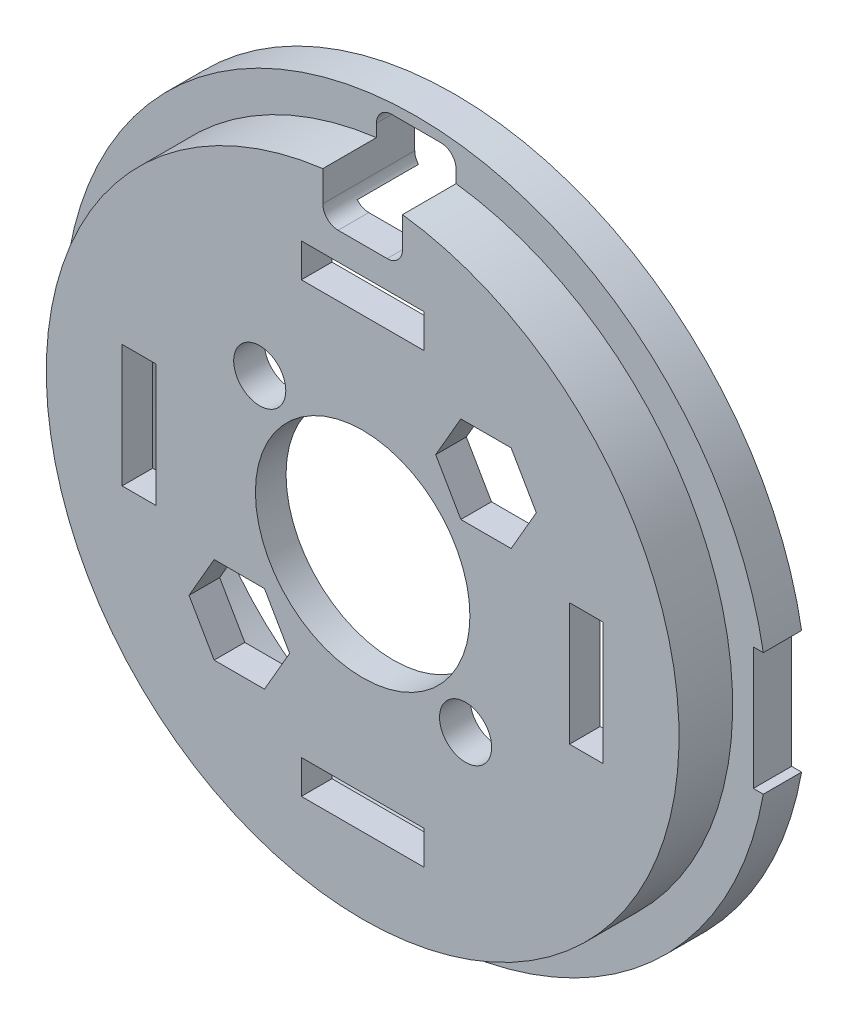
SolidWorks part; units mm, degrees
other "标注1"
sketch "草图10" plane through (17.4, 17.4, 7.6) normal (0.4476, 0.4282, 0.7851) x (0.8625, 0.025, -0.5054)
ref_plane "前视基准面" through (0, 0, 0) normal (0, 0, 1) x (1, 0, 0)
ref_plane "上视基准面" through (0, 0, 0) normal (0, 1, 0) x (1, 0, 0)
ref_plane "右视基准面" through (0, 0, 0) normal (1, 0, 0) x (0, 0, -1)
other "Configuration Table"
sketch "草图1" plane through (0, 0, 0) normal (0, 0, 1) x (1, 0, 0)
  circle A0 centre (0, 0) radius 17.4
  dimension "D1" = 34.8
extrude "凸台-拉伸1" add sketch "草图1" along normal blind 5.6
sketch "草图2" plane through (0, 0, 5.6) normal (0, 0, 1) x (1, 0, 0)
  line L0 (5.5154, -5.5154) -> (6.7175, -6.7175) construction
  line L1 (-6.7175, 6.7175) -> (-5.0175, 6.7175)
  line L2 (-6.7175, 6.7175) -> (-6.7175, 5.0175)
  line L3 (5.0175, -6.7175) -> (6.7175, -6.7175)
  line L4 (6.7175, -5.0175) -> (6.7175, -6.7175)
  line L5 (-6.7175, 6.7175) -> (-0.0325, 0.0325) construction
  line L6 (-6.7175, 6.7175) -> (6.7175, -6.7175)
  circle A0 centre (-6.7175, 6.7175) radius 1.7
  circle A2 centre (6.7175, -6.7175) radius 1.7
  arc A4 (-5.5154, -5.5154) -> (-6.7175, -5.0175) centre (-6.7175, -6.7175) ccw [skipped]
  arc A5 (5.0175, 6.7175) -> (5.5154, 5.5154) centre (6.7175, 6.7175) ccw [skipped]
  point P0 (0, 0)
  point P16 (0, 0)
  dimension "D3" = 3.4
  dimension "D1" = 19
  dimension "D2" = 9.5
  dimension "D4" = 4
extrude "切除-拉伸1" cut sketch "草图2" against normal through all contours A0 | A2
sketch "草图3" plane through (0, 0, 5.6) normal (0, 0, 1) x (1, 0, 0)
  circle A0 centre (0, 0) radius 7
  dimension "D1" = 14
extrude "切除-拉伸2" cut sketch "草图3" against normal through all
sketch "草图4" plane through (0, 0, 5.6) normal (0, 0, 1) x (1, 0, 0)
  circle A1 centre (-6.7175, 6.7175) radius 2.8
  circle A2 centre (6.7175, -6.7175) radius 2.8
  dimension "D1" = 5.6
  dimension "D2" = 5.6
extrude "切除-拉伸3" cut sketch "草图4" against normal blind 3
sketch "草图5" plane through (0, 0, 5.6) normal (0, 0, 1) x (1, 0, 0)
  line L1 (-8.05, 8) -> (8.05, 8)
  line L2 (-8.05, 8) -> (-8.05, -8)
  line L3 (-8.05, -8) -> (8.05, -8)
  line L4 (8.05, 8) -> (8.05, -8)
  line L5 (-8.05, 8) -> (8.05, -8) construction
  line L6 (-8.05, -8) -> (8.05, 8) construction
  circle A0 centre (8.05, 8) radius 1.7
  circle A1 centre (-8.05, -8) radius 1.7
  point P0 (0, 0)
  dimension "D3" = 3.4
  dimension "D4" = 3.4
  dimension "D1" = 16.1
  dimension "D2" = 16
extrude "切除-拉伸4" cut sketch "草图5" against normal through all contours A1 | A0
sketch "草图6" plane through (0, 0, 0) normal (0, 0, -1) x (-1, 0, 0)
  line L0 (4.7668, -8) -> (6.4084, -10.8433)
  line L1 (-4.7668, 8) -> (-6.4084, 10.8433)
  line L2 (-6.4084, 10.8433) -> (-9.6916, 10.8433)
  line L3 (-9.6916, 10.8433) -> (-11.3332, 8)
  line L4 (-11.3332, 8) -> (-9.6916, 5.1567)
  line L5 (-9.6916, 5.1567) -> (-6.4084, 5.1567)
  line L6 (-6.4084, 5.1567) -> (-4.7668, 8)
  line L7 (6.4084, -10.8433) -> (9.6916, -10.8433)
  line L8 (9.6916, -10.8433) -> (11.3332, -8)
  line L9 (11.3332, -8) -> (9.6916, -5.1567)
  line L10 (9.6916, -5.1567) -> (6.4084, -5.1567)
  line L11 (6.4084, -5.1567) -> (4.7668, -8)
  circle A0 centre (-8.05, 8) radius 2.8433 construction
  point P17 (0, 0)
  dimension "D1" = 2
extrude "切除-拉伸5" cut sketch "草图6" against normal blind 2.5
sketch "草图7" plane through (0, 0, 5.6) normal (0, 0, 1) x (1, 0, 0)
  line L5 (-8.05, 8.05) -> (8.05, 8.05)
  line L6 (-8.05, 8.05) -> (-8.05, -8.05)
  line L11 (-8.05, -8.05) -> (8.05, -8.05)
  line L12 (8.05, 8.05) -> (8.05, -8.05)
  line L13 (-8.05, 8.05) -> (8.05, -8.05) construction
  line L14 (-8.05, -8.05) -> (8.05, 8.05) construction
  point P0 (0, 0)
  dimension "D1" = 16.1
  dimension "D2" = 16.1
extrude "切除-拉伸6" cut sketch "草图7" against normal blind 1.5
chamfer "倒角1" distance 0.5 angle 45 4 edges at (1.0479, 8.05, 5.6) (8.05, 1.0226, 5.6) (-1.0479, -8.05, 5.6) (-8.05, -1.0226, 5.6)
sketch "草图8" plane through (0, 0, 0) normal (1, 0, 0) x (0, 0, -1)
  line L0 (0, 17.4) -> (0, 17.2)
  line L1 (0, 17.4) -> (0.2, 17.4)
  line L2 (0.2, 17.4) -> (0, 17.2)
  dimension "D1" = 0.2
  dimension "D2" = 0.2
ref_axis "基准轴1" through (0, 0, 0) along (0, 0, 1)
revolve "旋转1" add sketch "草图8" angle 360 about axis through (0, 0, 0) along (0, 0, 1)
sketch "草图9" plane through (0, 0, 5.6) normal (0, 0, 1) x (1, 0, 0)
  line L0 (0, 0) -> (15, 0) construction
  line L1 (4, -13.5) -> (-4, -13.5)
  line L2 (13.5, 4) -> (16.5, 4)
  line L3 (13.5, 4) -> (13.5, -4)
  line L4 (13.5, -4) -> (16.5, -4)
  line L5 (16.5, 4) -> (16.5, -4)
  line L6 (13.5, 4) -> (16.5, -4) construction
  line L7 (13.5, -4) -> (16.5, 4) construction
  line L8 (4, -13.5) -> (4, -16.5)
  line L9 (4, -16.5) -> (-4, -16.5)
  line L10 (-4, -13.5) -> (-4, -16.5)
  line L11 (-13.5, -4) -> (-13.5, 4)
  line L12 (-13.5, -4) -> (-16.5, -4)
  line L13 (-16.5, -4) -> (-16.5, 4)
  line L14 (-13.5, 4) -> (-16.5, 4)
  line L15 (-4, 13.5) -> (4, 13.5)
  line L16 (-4, 13.5) -> (-4, 16.5)
  line L17 (-4, 16.5) -> (4, 16.5)
  line L18 (4, 13.5) -> (4, 16.5)
  line L19 (15.7, 4) -> (15.7, -4)
  line L20 (4, -15.7) -> (-4, -15.7)
  line L21 (-15.7, -4) -> (-15.7, 4)
  line L22 (-4, 15.7) -> (4, 15.7)
  point P22 (0, 0)
  point P31 (0, 0)
  dimension "D1" = 15
  dimension "D2" = 3
  dimension "D3" = 8
  dimension "D5" = 0.8
  dimension "D4" = 4
  dimension "D6" = 4
extrude "切除-拉伸7" cut sketch "草图9" against normal through all contours L19 L2 L3 L4 | L22 L16 L15 L18 | L21 L12 L11 L14 | L20 L8 L1 L10 region at (0, -14.6, 5.6) region at (14.6, 0, 5.6) region at (-14.6, 0, 5.6) region at (0, 14.6, 5.6)
sketch "Sketch1" plane through (0, 0, 0) normal (0, 0, 1) x (1, 0, 0)
  circle A0 centre (0, 0) radius 17.4
  circle A1 centre (0, 0) radius 20.65
  dimension "D1" = 41.3
extrude "Boss-Extrude1" add sketch "Sketch1" along normal up to surface (5.6 mm away) and the other way blind 4 up to face at (0, 0, 5.6)
sketch "Sketch2" plane through (0, 0, -4) normal (0, 0, -1) x (-1, 0, 0)
  line L0 (0, 0) -> (-17.5, 0)
  line L1 (-17.5, 0) -> (-17.5, 4)
  line L2 (-17.5, 4) -> (-20, 4)
  line L3 (-20, 4) -> (-20, -4)
  line L4 (-20, -4) -> (-17.5, -4)
  line L5 (-17.5, -4) -> (-17.5, 0)
  dimension "D1" = 2.5
  dimension "D2" = 4
  dimension "D3" = 4
  dimension "D4" = 17.5
sketch "Sketch3" plane through (0, 0, -4) normal (0, 0, -1) x (-1, 0, 0)
  circle A0 centre (0, 0) radius 20.65
  circle A1 centre (0, 0) radius 23
  circle M10 centre (0, 0) radius 20.65
  dimension "D1" = 46
extrude "Boss-Extrude2" add sketch "Sketch3" against normal blind 2.5 contours A1 M10 region at (22.3495, 0, -4)
sketch "Sketch4" plane through (0, 0, -4) normal (0, 0, -1) x (-1, 0, 0)
  circle A0 centre (0, 0) radius 18
  dimension "D1" = 36
extrude "Cut-Extrude3" cut sketch "Sketch4" against normal up to surface (4 mm away) up to face at (0, 14.6, 0)
sketch "Sketch5" plane through (0, 0, -4) normal (0, 0, -1) x (-1, 0, 0)
  line L13 (0, 0) -> (23, 0)
  line L14 (0, 0) -> (-23, 0)
  line L15 (23, -4) -> (22, -4)
  line L16 (23, -4) -> (23, 4)
  line L17 (23, 4) -> (22, 4)
  line L18 (22, -4) -> (22, 4)
  line L19 (-23, 4) -> (-22, 4)
  line L20 (-23, 4) -> (-23, -4)
  line L21 (-23, -4) -> (-22, -4)
  line L22 (-22, 4) -> (-22, -4)
  circle A0 centre (0, 0) radius 23 construction
  point P9 (0, 22)
  point P19 (0, -22)
  point P23 (0, 0)
  point P34 (0, 0)
  dimension "D4" = 8
  dimension "D5" = 1
  dimension "D6" = 4
  dimension "D3" = 2
  dimension "D7" = 2
extrude "Cut-Extrude4" cut sketch "Sketch5" against normal blind 10 contours L19 L22 L21 L20 | L16 L15 L18 L17
sketch "Sketch7" plane through (0, 0, -4) normal (0, 0, -1) x (-1, 0, 0)
  line L1 (0, 22.3) -> (2.6, 22.3)
  line L2 (0, 17.5) -> (-2.6, 17.5)
  line L3 (0, 17.5) -> (0, 22.3)
  line L4 (0, 22.3) -> (-2.6, 22.3)
  line L5 (-2.6, 17.5) -> (-2.6, 22.3)
  line L7 (0, 22.3) -> (0, 17.5)
  line L10 (0, 22.3) -> (0, 17.5)
  line L11 (0, 17.5) -> (2.6, 17.5)
  line L12 (2.6, 22.3) -> (2.6, 17.5)
  circle M5 centre (0, 0) radius 18
  dimension "D1" = 2.6
  dimension "D2" = 2.6
  dimension "D3" = 4.8
extrude "Cut-Extrude6" cut sketch "Sketch7" against normal blind 10 contours L5 L3 L4 M5 | L5 L2 L3 M5 | L12 L1 L3 M5 | L12 L3 L11 M5 region at (-1.3094, 20.1182, -4) region at (1.3094, 20.1182, -4) region at (-1.2066, 17.7222, -4) region at (1.2066, 17.7222, -4)
fillet "Fillet3" radius 1 4 edges at (2.6, 22.3, -2.75) (-2.6, 22.3, -2.75) (-2.6, 17.5, 2.8) (2.6, 17.5, 2.8)
sketch "Sketch8" plane through (0, 0, 5.6) normal (0, 0, 1) x (1, 0, 0)
  circle A0 centre (0, 0) radius 23
sketch "Sketch9" plane through (0, 0, -4) normal (0, 0, -1) x (-1, 0, 0)
  circle A0 centre (0, 0) radius 23
sketch "Sketch10" plane through (0, 0, 5.6) normal (0, 0, 1) x (1, 0, 0)
  circle A0 centre (0, 0) radius 23
extrude "Cut-Extrude7" cut sketch "Sketch10" against normal blind 3.6
